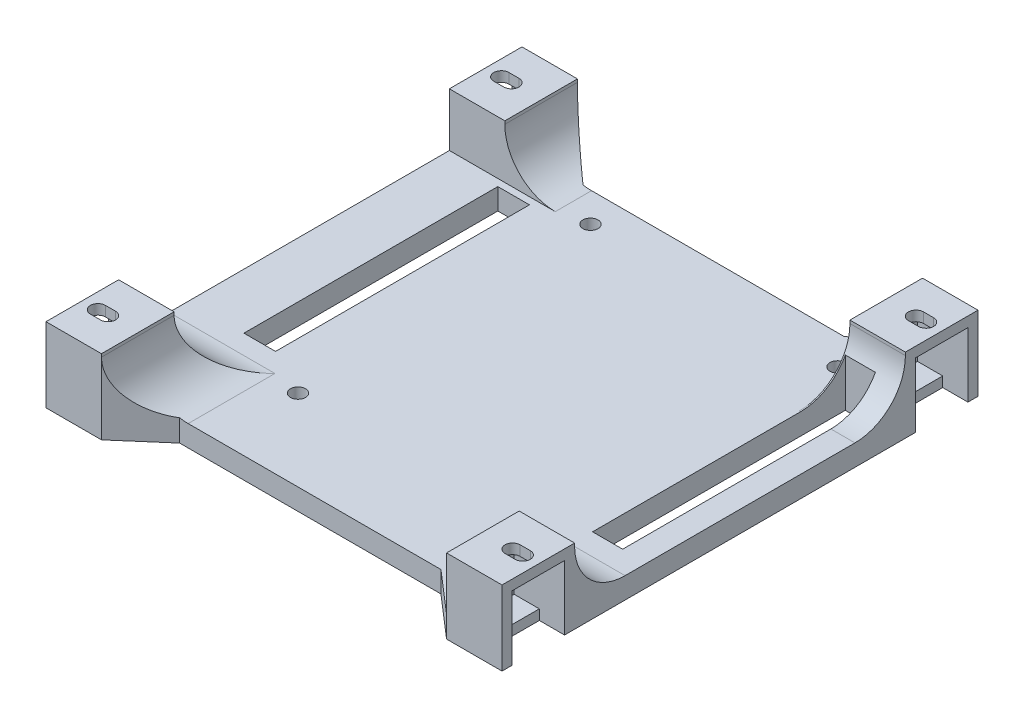
SolidWorks part; units mm, degrees
ref_plane "Front Plane" through (0, 0, 0) normal (0, 0, 1) x (1, 0, 0)
ref_plane "Top Plane" through (0, 0, 0) normal (0, 1, 0) x (1, 0, 0)
ref_plane "Right Plane" through (0, 0, 0) normal (1, 0, 0) x (0, 0, -1)
sketch "Sketch1" plane through (0, 0, 0) normal (1, 0, 0) x (0, 0, -1)
  line L0 (-18.2958, 19.4412) -> (-18.2958, 25.4412) construction
  line L2 (61.7042, 25.4412) -> (61.7042, 19.4412) construction
  line L5 (-18.2958, 22.4412) -> (61.7042, 22.4412) construction
  line L7 (-23.4958, 17.0412) -> (-13.0958, 17.0412)
  line L8 (-23.4958, 17.0412) -> (-23.4958, 27.8412)
  line L9 (-23.4958, 27.8412) -> (-13.0958, 27.8412)
  line L10 (-13.0958, 17.0412) -> (-13.0958, 27.8412)
  line L11 (-23.4958, 17.0412) -> (-13.0958, 27.8412) construction
  line L12 (-23.4958, 27.8412) -> (-13.0958, 17.0412) construction
  line L13 (56.5042, 17.0412) -> (66.9042, 17.0412)
  line L14 (56.5042, 17.0412) -> (56.5042, 27.8412)
  line L15 (56.5042, 27.8412) -> (66.9042, 27.8412)
  line L16 (66.9042, 17.0412) -> (66.9042, 27.8412)
  line L17 (56.5042, 17.0412) -> (66.9042, 27.8412) construction
  line L18 (56.5042, 27.8412) -> (66.9042, 17.0412) construction
  line L32 (-18.2958, 22.4412) -> (-78.2958, 22.4412) construction
  line L33 (-78.2958, 22.4412) -> (-78.2958, -17.0042) construction
  line L36 (-25.4958, 15.0412) -> (-11.0958, 15.0412)
  line L37 (-25.4958, 15.0412) -> (-25.4958, 29.8412)
  line L38 (-25.4958, 29.8412) -> (-11.0958, 29.8412)
  line L39 (-11.0958, 15.0412) -> (-11.0958, 29.8412)
  line L40 (-25.4958, 15.0412) -> (-11.0958, 29.8412) construction
  line L41 (-25.4958, 29.8412) -> (-11.0958, 15.0412) construction
  line L42 (54.5042, 29.8412) -> (68.9042, 29.8412)
  line L43 (54.5042, 29.8412) -> (54.5042, 15.0412)
  line L44 (54.5042, 15.0412) -> (68.9042, 15.0412)
  line L45 (68.9042, 29.8412) -> (68.9042, 15.0412)
  line L46 (54.5042, 29.8412) -> (68.9042, 15.0412) construction
  line L47 (54.5042, 15.0412) -> (68.9042, 29.8412) construction
  dimension "D1" = 10.4
  dimension "D3" = 10.4
  dimension "D4" = 10.8
  dimension "D9" = 2
  dimension "D10" = 2
  dimension "D11" = 2
  dimension "D12" = 2
extrude "Boss-Extrude1" add sketch "Sketch1" along normal blind 5
sketch "Sketch2" plane through (5, 0, 0) normal (1, 0, 0) x (0, 0, -1)
  line L0 (-25.4958, 29.8412) -> (-11.0958, 29.8412)
  line L1 (-11.0958, 29.8412) -> (-11.0958, 15.0412)
  line L2 (-25.4958, 29.8412) -> (-25.4958, 15.0412)
  line L3 (-23.4958, 27.8412) -> (-13.0958, 27.8412)
  line L4 (-13.0958, 27.8412) -> (-13.0958, 15.0412)
  line L5 (-25.4958, 15.0412) -> (-11.0958, 15.0412) construction
  line L6 (-13.0958, 15.0412) -> (-11.0958, 15.0412)
  line L7 (-23.4958, 27.8412) -> (-23.4958, 15.0412)
  line L8 (-23.4958, 15.0412) -> (-25.4958, 15.0412)
  line L9 (54.5042, 29.8412) -> (68.9042, 29.8412)
  line L10 (68.9042, 29.8412) -> (68.9042, 15.0412)
  line L11 (54.5042, 29.8412) -> (54.5042, 15.0412)
  line L12 (56.5042, 27.8412) -> (66.9042, 27.8412)
  line L13 (66.9042, 27.8412) -> (66.9042, 15.0412)
  line L14 (66.9042, 15.0412) -> (68.9042, 15.0412)
  line L15 (56.5042, 27.8412) -> (56.5042, 15.0412)
  line L16 (54.5042, 15.0412) -> (68.9042, 15.0412) construction
  line L17 (56.5042, 15.0412) -> (54.5042, 15.0412)
extrude "Boss-Extrude2" add sketch "Sketch2" along normal blind 5
sketch "Sketch3" plane through (0, 0, 0) normal (-1, 0, 0) x (0, 0, 1)
  line L1 (-68.9042, 29.8412) -> (-54.5042, 29.8412)
  line L2 (-68.9042, 29.8412) -> (-68.9042, 15.0412)
  line L3 (-68.9042, 15.0412) -> (-54.5042, 15.0412)
  line L4 (-54.5042, 29.8412) -> (-54.5042, 15.0412)
  line L5 (11.0958, 29.8412) -> (25.4958, 29.8412)
  line L6 (11.0958, 29.8412) -> (11.0958, 15.0412)
  line L7 (11.0958, 15.0412) -> (25.4958, 15.0412)
  line L8 (25.4958, 29.8412) -> (25.4958, 15.0412)
extrude "Boss-Extrude3" add sketch "Sketch3" along normal blind 1
sketch "Sketch4" plane through (-1, 0, 0) normal (-1, 0, 0) x (0, 0, 1)
  line L0 (-61.7042, 29.8412) -> (-61.7042, 15.0412) construction
  line L1 (-54.5042, 29.8412) -> (-68.9042, 29.8412) construction
  line L2 (-68.9042, 15.0412) -> (-54.5042, 15.0412) construction
  line L3 (18.2958, 29.8412) -> (18.2958, 15.0412) construction
  line L4 (25.4958, 29.8412) -> (11.0958, 29.8412) construction
  line L5 (11.0958, 15.0412) -> (25.4958, 15.0412) construction
  line L6 (-61.7042, 15.0412) -> (18.2958, 15.0412)
  line L7 (18.2958, 15.0412) -> (18.2958, 19.2412)
  line L8 (18.2958, 19.2412) -> (-61.7042, 19.2412)
  line L9 (-61.7042, 19.2412) -> (-61.7042, 15.0412)
extrude "Boss-Extrude4" add sketch "Sketch4" along normal blind 34.22
sketch "Sketch19" plane through (0, 29.8412, 0) normal (0, 1, 0) x (1, 0, 0)
  line L0 (10, 61.7042) -> (-1, 61.7042) construction
  line L1 (10, 68.9042) -> (10, 54.5042) construction
  line L2 (-1, 54.5042) -> (-1, 68.9042) construction
  line L3 (4.9011, 61.7042) -> (6.9011, 61.7042) construction
  line L4 (4.9011, 63.2042) -> (6.9011, 63.2042)
  line L5 (4.9011, 60.2042) -> (6.9011, 60.2042)
  line L6 (4.5, 54.5042) -> (4.5, -11.0958) construction
  line L7 (10, 54.5042) -> (-1, 54.5042) construction
  line L8 (10, -11.0958) -> (-1, -11.0958) construction
  line L9 (4.5, 21.7042) -> (-35.22, 21.7042) construction
  line L10 (-35.22, -18.2958) -> (-35.22, 61.7042) construction
  line L11 (4.9011, -18.2958) -> (6.9011, -18.2958) construction
  line L12 (4.9011, -19.7958) -> (6.9011, -19.7958)
  line L13 (4.9011, -16.7958) -> (6.9011, -16.7958)
  arc A0 (4.9011, 63.2042) -> (4.9011, 60.2042) centre (4.9011, 61.7042) ccw
  arc A1 (6.9011, 60.2042) -> (6.9011, 63.2042) centre (6.9011, 61.7042) ccw
  arc A2 (4.9011, -19.7958) -> (4.9011, -16.7958) centre (4.9011, -18.2958) cw
  arc A3 (6.9011, -16.7958) -> (6.9011, -19.7958) centre (6.9011, -18.2958) cw
  point P8 (5.9011, 61.7042)
  point P25 (5.9011, -18.2958)
  dimension "D1" = 2
extrude "Cut-Extrude9" cut sketch "Sketch19" against normal blind 5
sketch "Sketch20" plane through (0, 19.2412, 0) normal (0, 1, 0) x (1, 0, 0)
  line L0 (-1, -11.0958) -> (10, -11.0958)
  line L1 (10, -11.0958) -> (10, 54.5042)
  line L2 (10, 54.5042) -> (-1, 54.5042)
  line L3 (-1, 54.5042) -> (-1, -11.0958)
extrude "Boss-Extrude8" add sketch "Sketch20" against normal up to surface (4.2 mm away) up to face at (1.178, 15.0412, -21.7042)
mirror "Mirror1" about plane through (-35.22, 0, 0) normal (-1, 0, 0) of bodies 141 139
sketch "Sketch9" plane through (0, 19.2412, 0) normal (0, 1, 0) x (1, 0, 0)
  line L0 (-1, 68.9042) -> (-1, 61.7042)
  line L1 (-1, 54.5042) -> (-1, 68.9042) construction
  line L2 (-1, 61.7042) -> (-9.311, 61.7042)
  line L3 (-69.44, 61.7042) -> (-1, 61.7042) construction
  line L4 (-9.311, 61.7042) -> (-1, 68.9042)
  line L5 (-35.22, 61.7042) -> (-35.22, 81.0456) construction
  line L6 (-61.129, 61.7042) -> (-69.44, 68.9042)
  line L7 (-69.44, 61.7042) -> (-61.129, 61.7042)
  line L8 (-69.44, 68.9042) -> (-69.44, 61.7042)
  line L9 (10, 21.7042) -> (-50.0448, 21.7042) construction
  line L11 (-69.44, -25.4958) -> (-69.44, -18.2958)
  line L12 (-69.44, -18.2958) -> (-61.129, -18.2958)
  line L13 (-61.129, -18.2958) -> (-69.44, -25.4958)
  line L14 (-9.311, -18.2958) -> (-1, -25.4958)
  line L15 (-1, -18.2958) -> (-9.311, -18.2958)
  line L16 (-1, -25.4958) -> (-1, -18.2958)
  line L17 (10, -11.0958) -> (10, 54.5042) construction
extrude "Boss-Extrude7" add sketch "Sketch9" against normal up to surface (4.2 mm away) up to face at (-35.22, 15.0412, -21.7042)
sketch "Sketch12" plane through (0, 19.2412, 0) normal (0, 1, 0) x (1, 0, 0)
  circle A0 centre (-4.7838, -2.1732) radius 1.5
  circle A1 centre (-53.7838, -2.1732) radius 1.5
  circle A2 centre (-53.7838, 55.8268) radius 1.5
  circle A3 centre (-4.7838, 55.8268) radius 1.5
extrude "Cut-Extrude2" cut sketch "Sketch12" against normal blind 10
sketch "Sketch13" plane through (0, 19.2412, 0) normal (0, 1, 0) x (1, 0, 0)
  line L1 (-0.7503, 3.2111) -> (5.219, 3.2111)
  line L2 (-0.7503, 3.2111) -> (-0.7503, 53.3377)
  line L3 (-0.7503, 53.3377) -> (5.219, 53.3377)
  line L4 (5.219, 3.2111) -> (5.219, 53.3377)
extrude "Cut-Extrude3" cut sketch "Sketch13" against normal blind 10
sketch "Sketch14" plane through (0, 19.2412, 0) normal (0, 1, 0) x (1, 0, 0)
  line L1 (-63.1677, 2.759) -> (-69.44, 2.759)
  line L2 (-63.1677, 2.759) -> (-63.1677, 53.1122)
  line L3 (-63.1677, 53.1122) -> (-69.44, 53.1122)
  line L4 (-69.44, 2.759) -> (-69.44, 53.1122)
extrude "Cut-Extrude4" cut sketch "Sketch14" against normal blind 10
fillet "Fillet2" radius 10 5 edges at (4.5, 19.2412, 11.0958) (-74.94, 19.2412, 11.0958) (4.5, 19.2412, -54.5042) (-69.44, 19.2412, 18.2958) (-69.44, 19.2412, -61.7042)
